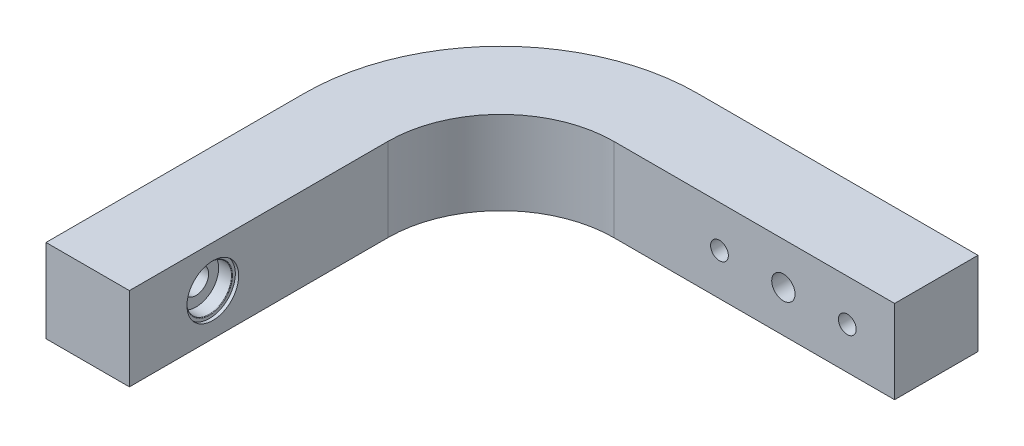
SolidWorks part; units mm, degrees
ref_plane "Front Plane" through (0, 0, 0) normal (0, 0, 1) x (1, 0, 0)
ref_plane "Top Plane" through (0, 0, 0) normal (0, 1, 0) x (1, 0, 0)
ref_plane "Right Plane" through (0, 0, 0) normal (1, 0, 0) x (0, 0, -1)
ref_axis "Z" through (0, 0, -59.2654) along (0, 0, 1)
sketch "Sketch1" plane through (0, 0, 0) normal (0, 1, 0) x (1, 0, 0)
  line L0 (-30.4827, 0) -> (30.4827, 0) construction
  line L1 (-65.8046, -35.3218) -> (-65.8046, -81.8046)
  line L2 (-65.8046, -81.8046) -> (-50.8046, -81.8046)
  line L3 (-50.8046, -81.8046) -> (-50.8046, -35.3218)
  line L4 (-30.4827, -15) -> (30.4827, -15) construction
  line L5 (0, -15) -> (0, 0) construction
  line L6 (50.8046, -81.8046) -> (50.8046, -35.3218) construction
  line L7 (65.8046, -81.8046) -> (50.8046, -81.8046) construction
  line L8 (65.8046, -35.3218) -> (65.8046, -81.8046) construction
  line L9 (30.4827, 0) -> (30.4827, -15) construction
  line L10 (20, -15) -> (20, 0)
  line L11 (-30.4827, -15) -> (20, -15)
  line L12 (-30.4827, 0) -> (20, 0)
  line L13 (0, 59.2654) -> (0, -30.9346) construction
  arc A0 (-30.4827, 0) -> (-65.8046, -35.3218) centre (-30.4827, -35.3218) ccw
  arc A1 (-50.8046, -35.3218) -> (-30.4827, -15) centre (-30.4827, -35.3218) cw
  arc A2 (50.8046, -35.3218) -> (30.4827, -15) centre (30.4827, -35.3218) ccw construction
  arc A3 (30.4827, 0) -> (65.8046, -35.3218) centre (30.4827, -35.3218) cw construction
  dimension "D3" = 20.3218
  dimension "D1" = 101.6092
  dimension "D2" = 15
  dimension "D4" = 66.8046
  dimension "D5" = 20
extrude "Boss-Extrude1" add sketch "Sketch1" along normal blind 7.5 and the other way blind 7.5
sketch "Sketch2" plane through (-50.8046, 0, 0) normal (-1, 0, 0) x (0, 0, 1)
  line L1 (45.1, 0) -> (-45.1, 0) construction
  line L2 (0, -8.25) -> (0, 8.25) construction
  circle A0 centre (66.8046, 0) radius 2.25
  dimension "D1" = 4.5
  dimension "D2" = 66.8046
extrude "Cut-Extrude1" cut sketch "Sketch2" against normal through all both and the other way through all
ref_axis "Axis2" through (-85.4136, 0, 66.8046) along (1, 0, 0)
sketch "Sketch3" plane through (0, 0, 0) normal (0, 0, -1) x (-1, 0, 0)
  line L0 (-11.5, 0) -> (11.5, 0) construction
  circle A0 centre (0, 0) radius 2.1
  circle A1 centre (-11.5, 0) radius 1.6
  circle A2 centre (11.5, 0) radius 1.6
  dimension "D1" = 4.2
  dimension "D3" = 3.2
  dimension "D2" = 23
extrude "Cut-Extrude2" cut sketch "Sketch3" against normal through all
sketch "Sketch5" plane through (0, 0, 0) normal (0, 1, 0) x (1, 0, 0)
  line L0 (-65.8046, -71.4546) -> (-65.2046, -71.4546)
  line L1 (-65.2046, -71.4546) -> (-65.2046, -70.9546)
  line L2 (-65.1046, -70.8546) -> (-62.8046, -70.8546)
  line L3 (-62.8046, -70.8546) -> (-62.8046, -66.8046)
  line L4 (-65.8046, -71.4546) -> (-65.8046, -66.8046)
  line L5 (-85.4136, -66.8046) -> (-36.6951, -66.8046) construction
  line L6 (-84.3923, -66.8046) -> (-79.5242, -66.8046) construction
  line L7 (-65.8046, -66.8046) -> (-62.8046, -66.8046)
  line L9 (-65.8046, -35.3218) -> (-65.8046, -81.8046) construction
  line L10 (-58.3046, -77.8481) -> (-58.3046, -69.6196) construction
  line L11 (-65.8046, -81.8046) -> (-50.8046, -81.8046) construction
  line L12 (-50.8046, -66.8046) -> (-53.8046, -66.8046)
  line L13 (-50.8046, -71.4546) -> (-50.8046, -66.8046)
  line L14 (-53.8046, -70.8546) -> (-53.8046, -66.8046)
  line L15 (-51.5046, -70.8546) -> (-53.8046, -70.8546)
  line L16 (-51.4046, -71.4546) -> (-51.4046, -70.9546)
  line L17 (-50.8046, -71.4546) -> (-51.4046, -71.4546)
  arc A0 (-65.1046, -70.8546) -> (-65.2046, -70.9546) centre (-65.1046, -70.9546) ccw
  arc A1 (-51.5046, -70.8546) -> (-51.4046, -70.9546) centre (-51.5046, -70.9546) cw
  point P14 (-58.3046, -81.8046)
  point P25 (-65.2046, -70.8546)
  point P28 (-51.4046, -70.8546)
  dimension "D5" = 0.1
  dimension "D6" = 0.1
  dimension "D1" = 0.6
  dimension "D2" = 4.65
  dimension "D3" = 8.1
  dimension "D4" = 3
revolve "bearing-seats" cut sketch "Sketch5" angle 360 about L6
equation "\"width\"= \"EyeDiameter\" + \"EyeClearance\""
equation "\"prongwidth\"= \"L2Thickness\""
equation "\"D2@Sketch1\"=\"prongwidth\""
equation "\"D3@Sketch1\"=\"width\"/5"
equation "\"pronglength\"= \"BasePlaneDistance\"'model implicitly adds clearance (of prongwidth) to the hole drilled at the baseplanedistance"
equation "\"D4@Sketch1\"=\"pronglength\""
equation "\"D1@Boss-Extrude1\"=\"prongwidth\"/2"
equation "\"D2@Boss-Extrude1\"=\"prongwidth\"/2"
equation "\"lbracket-plane-to-axis\"= \"BasePlaneDistance\""
equation "\"D2@Sketch2\"=\"lbracket-plane-to-axis\""
equation "\"EyeDiameter\" = 99.60916292"
equation "\"BasePlaneDistance\" = \"EyeDiameter\"/2+\"L2Thickness\"+\"EyeClearance\""
equation "\"EyeClearance\" = 2"
equation "\"D1@Sketch1\"=\"EyeDiameter\"+\"EyeClearance\""
equation "\"BearingDepth\"= 6"
equation "\"BearingHousingID\"=4.5"
equation "\"BearingFlangeThickness\"= 0.75"
equation "\"BearingFlangeOD\"=7.5"
equation "\"PrinterFilamentThickness\"= 0.1"
equation "\"ApplyPrinterOffset\"= 1'if 1, adjust hole sizes to try and make pressfits work with the 3d printer"
equation "\"L2Thickness\" = 3.75 * \"shaft_diameter\""
equation "\"L2_ID\" = 20"
equation "\"vx\" = 50"
equation "\"vy\" = 10"
equation "\"vz\" = 100"
equation "\"parametric_end\" = 1"
equation "\"Rw_3_xx\" = -(\"vz\")/sqr((\"vx\")^2 + (\"vz\")^2)"
equation "\"Rw_3_xy\" = 0"
equation "\"Rw_3_xz\" = (\"vx\")/sqr((\"vx\")^2 + (\"vz\")^2)"
equation "\"Rw_3_zx\" = (\"vx\")/sqr((\"vx\")^2 + (\"vy\")^2 + (\"vz\")^2)"
equation "\"Rw_3_zy\" = (\"vy\")/sqr((\"vx\")^2 + (\"vy\")^2 + (\"vz\")^2)"
equation "\"Rw_3_zz\" = (\"vz\")/sqr((\"vx\")^2 + (\"vy\")^2 + (\"vz\")^2)"
equation "\"Rw_3_yx\" = (\"vx\")*(\"vy\")/sqr((\"vx\")^4 + (\"vx\")^2*(\"vy\")^2 + 2*(\"vx\")^2*(\"vz\")^2 + (\"vy\")^2*(\"vz\")^2 + (\"vz\")^4)"
equation "\"Rw_3_yy\" = -sqr((\"vx\")^2 + (\"vz\")^2)/sqr((\"vx\")^2 + (\"vy\")^2 + (\"vz\")^2)"
equation "\"Rw_3_yz\" = (\"vy\")*(\"vz\")/sqr((\"vx\")^4 + (\"vx\")^2*(\"vy\")^2 + 2*(\"vx\")^2*(\"vz\")^2 + (\"vy\")^2*(\"vz\")^2 + (\"vz\")^4)"
equation "\"O2Targx\" = -\"BasePlaneDistance\"*(\"vx\")*(\"vy\")/sqr((\"vx\")^4 + (\"vx\")^2*(\"vy\")^2 + 2*(\"vx\")^2*(\"vz\")^2 + (\"vy\")^2*(\"vz\")^2 + (\"vz\")^4)"
equation "\"O2Targy\" = \"BasePlaneDistance\"*sqr((\"vx\")^2 + (\"vz\")^2)/sqr((\"vx\")^2 + (\"vy\")^2 + (\"vz\")^2)"
equation "\"O2Targz\" = -\"BasePlaneDistance\"*(\"vy\")*(\"vz\")/sqr((\"vx\")^4 + (\"vx\")^2*(\"vy\")^2 + 2*(\"vx\")^2*(\"vz\")^2 + (\"vy\")^2*(\"vz\")^2 + (\"vz\")^4)"
equation "\"O2Targx_0\" = -(\"BasePlaneDistance\")*sqr((\"vx\")^2 + (\"vz\")^2)/sqr((\"vx\")^2 + (\"vy\")^2 + (\"vz\")^2)"
equation "\"O2Targy_0\" = -(\"BasePlaneDistance\")*(\"vy\")*(\"vz\")/sqr((\"vx\")^4 + (\"vx\")^2*(\"vy\")^2 + 2*(\"vx\")^2*(\"vz\")^2 + (\"vy\")^2*(\"vz\")^2 + (\"vz\")^4)"
equation "\"O2Targz_0\" = (\"BasePlaneDistance\")*(\"vx\")*(\"vy\")/sqr((\"vx\")^4 + (\"vx\")^2*(\"vy\")^2 + 2*(\"vx\")^2*(\"vz\")^2 + (\"vy\")^2*(\"vz\")^2 + (\"vz\")^4) + (\"BasePlaneDistance\")"
equation "\"theta2_s1\" = arcsin(((\"BasePlaneDistance\") - (\"O2Targz_0\"))/(\"BasePlaneDistance\")) + pi"
equation "\"theta2_s2\" = -arcsin(((\"BasePlaneDistance\") - (\"O2Targz_0\"))/(\"BasePlaneDistance\"))"
equation "\"theta1_s1\" = arcsin((\"O2Targy_0\")/((\"BasePlaneDistance\")*cos((\"Theta2\")))) + pi"
equation "\"theta1_s2\" = -arcsin((\"O2Targy_0\")/((\"BasePlaneDistance\")*cos((\"Theta2\"))))"
equation "\"theta1_s3\" = -arccos(-(\"O2Targx_0\")/((\"BasePlaneDistance\")*cos((\"Theta2\")))) + 2*pi"
equation "\"theta1_s4\" = arccos(-(\"O2Targx_0\")/((\"BasePlaneDistance\")*cos((\"Theta2\"))))"
equation "\"Theta1\" = \"theta1_s2\" 'so far, theta1_s1 and theta1_s4 have agreed, and they agree with the sw constraint solver"
equation "\"Theta2\" = \"theta2_s2\""
equation "\"o2_x\" = -(\"BasePlaneDistance\")*cos((\"Theta1\"))*cos((\"Theta2\"))"
equation "\"o2_y\" = -(\"BasePlaneDistance\")*sin((\"Theta1\"))*cos((\"Theta2\"))"
equation "\"o2_z\" = (\"BasePlaneDistance\")*(sin((\"Theta2\")) + 1)"
equation "\"o1_x\" = (\"BasePlaneDistance\")*sin((\"Theta1\"))"
equation "\"o1_y\" = -(\"BasePlaneDistance\")*cos((\"Theta1\"))"
equation "\"o1_z\" = (\"BasePlaneDistance\")"
equation "\"Actuator1_Theta\" = atn(\"vx\"/\"vz\") 'ik solution for the single link joint"
equation "\"Actuator2_Theta\" = \"Theta1\"  'ik solution for the double link joint"
equation "\"MotorBaseThickness\" = 3 "
equation "\"BaseThickness\" = 3 "
equation "\"EncoderToMagnetAirgap\" = 1 'Encoder to magnet airgap"
equation "\"EncoderHeight\" = 1.192  'Height of the encoder"
equation "\"MagnetThickness\" = 0.5  'Magnet thickness"
equation "\"pcb_thickness\" = 1.6  'Thickness of the PCB"
equation "\"pcb_outer_diameter\" = 32 'the OD of the pcb"
equation "\"shaft_diameter\" = 4"
equation "\"D1@Sketch2\"=\"shaft_diameter\"*1.125"
equation "\"D2@Sketch5\"=\"ApplyPrinterOffset\" * \"PrinterFilamentThickness\" / 2 + 4.6"
equation "\"D3@Sketch5\"= \"ApplyPrinterOffset\" * \"PrinterFilamentThickness\"  + 8.00"
